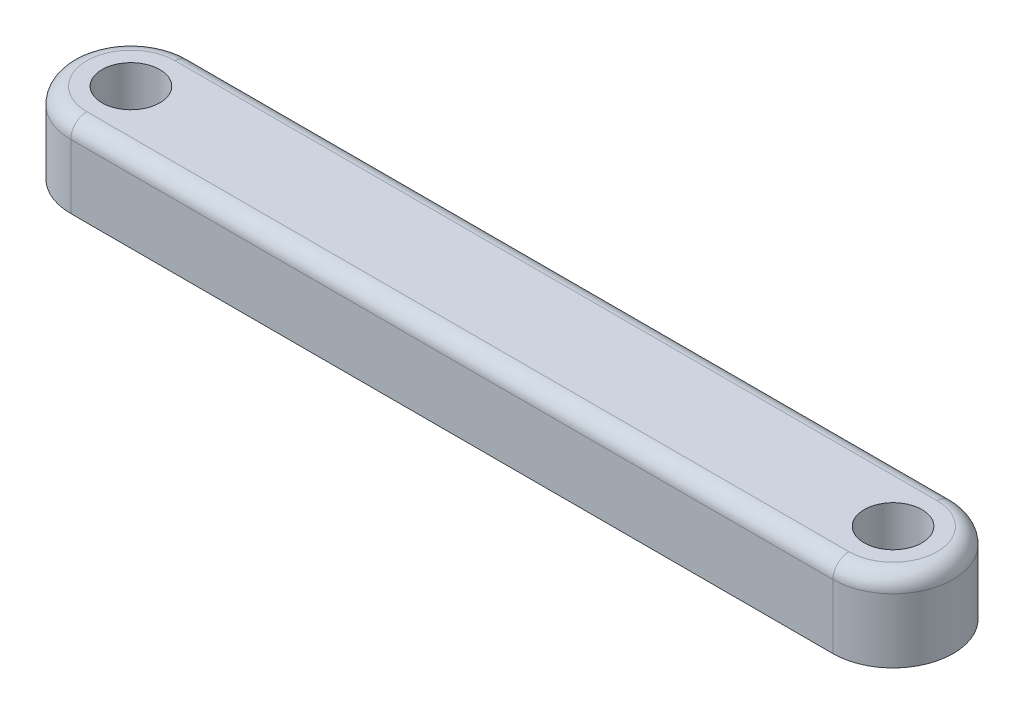
SolidWorks part; units mm, degrees
ref_plane "Front Plane" through (0, 0, 0) normal (0, 0, 1) x (1, 0, 0)
ref_plane "Top Plane" through (0, 0, 0) normal (0, 1, 0) x (1, 0, 0)
ref_plane "Right Plane" through (0, 0, 0) normal (1, 0, 0) x (0, 0, -1)
sketch "Sketch1" plane through (0, 0, 0) normal (0, 1, 0) x (1, 0, 0)
  line L0 (0, 0) -> (-60.325, 0) construction
  line L1 (0, -4.7625) -> (-60.325, -4.7625)
  line L2 (0, 4.7625) -> (-60.325, 4.7625)
  arc A0 (0, -4.7625) -> (0, 4.7625) centre (0, 0) ccw
  arc A1 (-60.325, 4.7625) -> (-60.325, -4.7625) centre (-60.325, 0) ccw
  circle A2 centre (-60.325, 0) radius 2.286
  circle A3 centre (0, 0) radius 2.286
  point P3 (-30.1625, 0)
  dimension "D1" = 4.572
  dimension "D2" = 4.7625
  dimension "D3" = 60.325
extrude "Boss-Extrude1" add sketch "Sketch1" along normal blind 6.35
fillet "Fillet1" radius 1.27 4 edges at (4.7625, 6.35, 0) (-30.1625, 6.35, 4.7625) (-65.0875, 6.35, 0) (-30.1625, 6.35, -4.7625)
